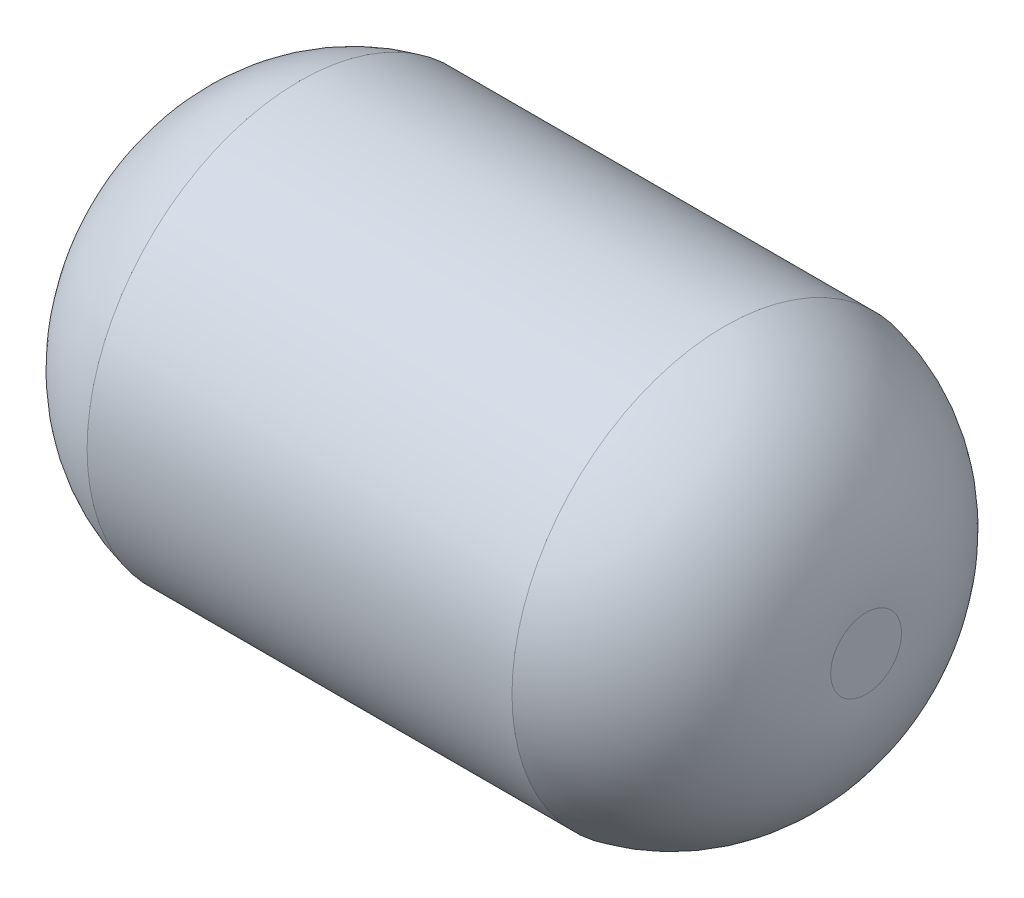
SolidWorks part; units mm, degrees
ref_plane "Front Plane" through (0, 0, 0) normal (0, 0, 1) x (1, 0, 0)
ref_plane "Top Plane" through (0, 0, 0) normal (0, 1, 0) x (1, 0, 0)
ref_plane "Right Plane" through (0, 0, 0) normal (1, 0, 0) x (0, 0, -1)
sketch "Sketch1" plane through (0, 0, 0) normal (0, 1, 0) x (1, 0, 0)
  line L0 (0, 0) -> (100, 0) construction
  line L1 (0, 0) -> (0, 60) construction
  line L2 (0, 60) -> (60, 60)
  line L3 (100, 0) -> (100, 10)
  line L4 (0, 59) -> (59.8963, 59)
  line L5 (99, 0) -> (99, 10.0079)
  arc A0 (60, 60) -> (100, 10) centre (49.7391, 10.7913) cw
  arc A1 (59.8963, 59) -> (99, 10.0079) centre (49.7391, 10.7913) cw
  arc A2 (60, 60) -> (100, 10) centre (49.7391, 10.7913) cw construction
  point P6 (49.7391, 10.7913)
  point P12 (0, 0)
  dimension "D1" = 100
  dimension "D2" = 60
  dimension "D3" = 10
  dimension "D5" = 60
  dimension "D4" = 1
revolve "Revolve-Thin1" add sketch "Sketch1" angle 360 about L0 wall 1
mirror "Mirror1" about plane through (0, 0, -59) normal (-1, 0, 0) of "Revolve-Thin1"
